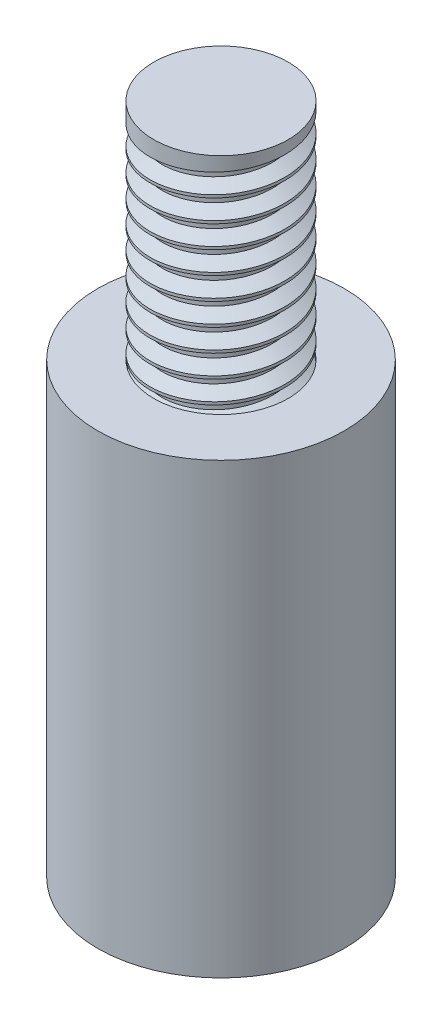
SolidWorks part; units mm, degrees
ref_plane "Alzado" through (0, 0, 0) normal (0, 0, 1) x (1, 0, 0)
ref_plane "Planta" through (0, 0, 0) normal (0, 1, 0) x (1, 0, 0)
ref_plane "Vista lateral" through (0, 0, 0) normal (1, 0, 0) x (0, 0, -1)
sketch "Croquis2" plane through (0, 0, 0) normal (0, 0, 1) x (1, 0, 0)
  line L0 (-65.9561, 0) -> (-65.9561, 10)
  line L1 (-65.9561, 5) -> (-63.2061, 5) construction
  line L2 (-65.9561, 0) -> (-64.7061, 0)
  line L3 (-64.7061, 0) -> (-64.7061, 3)
  line L4 (-64.7061, 3) -> (-63.2061, 3)
  line L5 (-63.2061, 3) -> (-63.2061, 10)
  line L6 (-63.2061, 10) -> (-63.2061, 15)
  line L7 (-63.2061, 15) -> (-64.7061, 15)
  line L8 (-64.7061, 15) -> (-64.7061, 10)
  line L9 (-64.7061, 10) -> (-65.9561, 10)
revolve "Revolución1" add sketch "Croquis2" angle 360 about L6
thread "Rosca2" pitch 0.5 method cut profile "Perfil de rosca3" start angle 0, offset 0, length 0, pitch 0.5, diameter 3
ref_plane "Plano3" through (-64.7061, 15, 0) normal (0, 0, 1) x (-1, 0, 0)
sketch "Perfil de rosca3" plane through (-64.7061, 15, 0) normal (0, 0, 1) x (-1, 0, 0)
  line L0 (0, 0) -> (0, 0.5) construction
  line L11 (0, 0) -> (0, 0.4375)
  line L12 (0, 0.4375) -> (-0.2706, 0.2812)
  line L13 (-0.2706, 0.2812) -> (-0.2706, 0.1562)
  line L15 (-0.2706, 0.1562) -> (0, 0)
  line L17 (-0.2706, 0.2187) -> (0, 0.2187) construction
  point P2 (0, 0)
  dimension "Pitch" = 0.5
  dimension "Profile_Angle" = 60
  dimension "Profile_Land" = 0.125
  dimension "Profile_Height" = 0.2706
thread "Rosca3" pitch 0.5 method extrude profile "Perfil de rosca4" start angle 0, offset 0, length 0, pitch 0.5, diameter 3
ref_plane "Plano4" through (-61.7061, 0, 0) normal (0, 0, 1) x (1, 0, 0)
sketch "Perfil de rosca4" plane through (-61.7061, 0, 0) normal (0, 0, 1) x (1, 0, 0)
  line L0 (0, 0) -> (0, 0.5) construction
  line L11 (0, 0) -> (0, 0.4375)
  line L12 (0, 0.4375) -> (-0.2706, 0.2812)
  line L13 (-0.2706, 0.2812) -> (-0.2706, 0.1562)
  line L15 (-0.2706, 0.1562) -> (0, 0)
  line L17 (-0.2706, 0.2187) -> (0, 0.2187) construction
  point P2 (0, 0)
  dimension "Pitch" = 0.5
  dimension "Profile_Angle" = 60
  dimension "Profile_Land" = 0.125
  dimension "Profile_Height" = 0.2706
